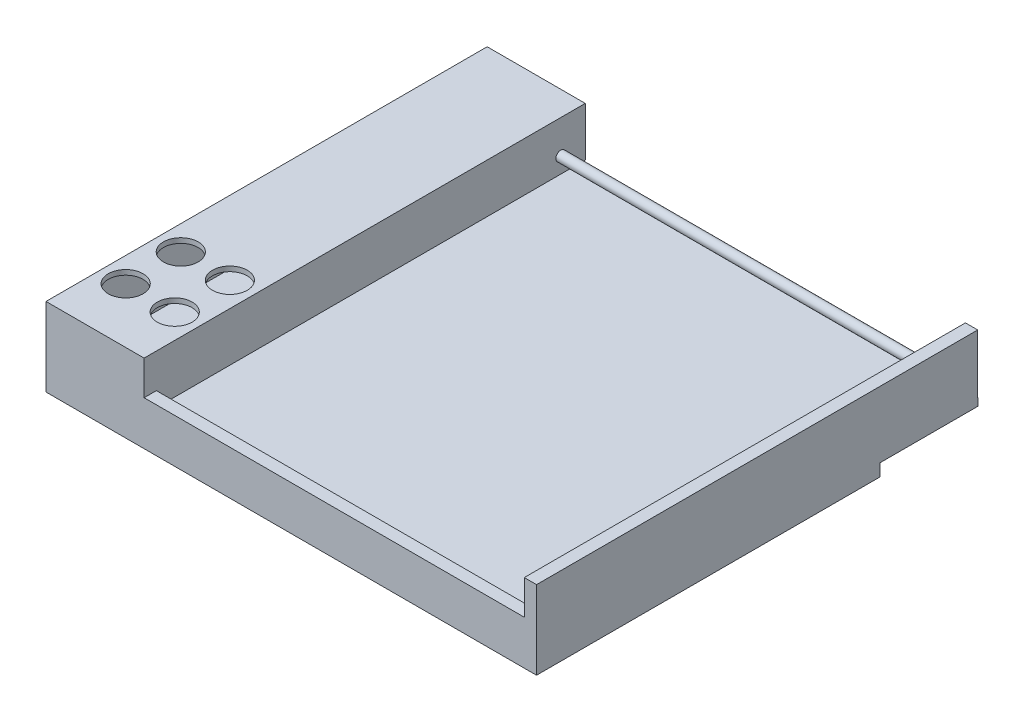
SolidWorks part; units mm, degrees
ref_plane "Front Plane" through (0, 0, 0) normal (0, 0, 1) x (1, 0, 0)
ref_plane "Top Plane" through (0, 0, 0) normal (0, 1, 0) x (1, 0, 0)
ref_plane "Right Plane" through (0, 0, 0) normal (1, 0, 0) x (0, 0, -1)
sketch "Sketch1" plane through (0, 0, 0) normal (0, 1, 0) x (1, 0, 0)
  line L1 (-100, -90) -> (100, -90)
  line L2 (-100, -90) -> (-100, 90)
  line L3 (-100, 90) -> (100, 90)
  line L4 (100, -90) -> (100, 90)
  line L5 (-100, -90) -> (100, 90) construction
  line L6 (-100, 90) -> (100, -90) construction
  point P0 (0, 0)
  dimension "D1" = 200
  dimension "D2" = 180
extrude "Boss-Extrude1" add sketch "Sketch1" along normal blind 3
sketch "Sketch2" plane through (0, 0, 0) normal (0, -1, 0) x (1, 0, 0)
  line L0 (-100, 90) -> (100, 90)
  line L1 (-100, 90) -> (-100, -50)
  line L2 (100, 90) -> (100, -50)
  line L3 (-100, -50) -> (100, -50)
  dimension "D1" = 140
extrude "Boss-Extrude2" add sketch "Sketch2" along normal blind 5
sketch "Sketch6" plane through (0, 3, 0) normal (0, 1, 0) x (1, 0, 0)
  line L0 (-100, -90) -> (100, -90)
  line L1 (-100, -90) -> (-100, 89.8697)
  line L2 (100, -90) -> (100, 89.8697)
  line L3 (-100, 89.8697) -> (100, 89.8697)
extrude "Boss-Extrude3" add sketch "Sketch6" along normal blind 24
sketch "Sketch7" plane through (0, 0, -89.8697) normal (0, 0, -1) x (-1, 0, 0)
  line L0 (-100, 15) -> (100, 15) construction
  line L1 (-100, 27) -> (-100, 3) construction
  line L2 (100, 27) -> (100, 3) construction
  line L3 (-100, 27) -> (100, 27) construction
  line L4 (-95, 3) -> (60, 3)
  line L5 (-95, 3) -> (-95, 27)
  line L6 (-95, 27) -> (60, 27)
  line L7 (60, 3) -> (60, 27)
  line L8 (-95, 3) -> (60, 27) construction
  line L9 (-95, 27) -> (60, 3) construction
  point P6 (-17.5, 15)
  dimension "D1" = 155
  dimension "D2" = 5
extrude "Cut-Extrude1" cut sketch "Sketch7" against normal up to surface (179.8697 mm away) up to face at (0, 11, 90)
sketch "Sketch8" plane through (95, 0, 0) normal (-1, 0, 0) x (0, 0, 1)
  line L0 (90, 3) -> (-89.8697, 3) construction
  line L1 (-89.8697, 27) -> (-89.8697, 3) construction
  circle A0 centre (-79.8697, 13.5) radius 2
  dimension "D3" = 4
  dimension "D1" = 10.5
  dimension "D2" = 10
extrude "Boss-Extrude4" add sketch "Sketch8" along normal up to surface (155 mm away) up to face at (-60, 15, 0.0651)
sketch "Sketch9" plane through (0, 3, 0) normal (0, 1, 0) x (1, 0, 0)
  line L0 (95, -90) -> (95, 89.8697) construction
  line L1 (-60, -90) -> (95, -90)
  line L2 (-60, -90) -> (-60, -85)
  line L3 (-60, -85) -> (95, -85)
  line L4 (95, -90) -> (95, -85)
  dimension "D1" = 5
extrude "Boss-Extrude5" add sketch "Sketch9" along normal blind 10
sketch "Sketch11" plane through (0, 0, -89.8697) normal (0, 0, -1) x (-1, 0, 0)
  line L0 (60, 3) -> (98, 3)
  line L1 (60, 3) -> (100, 3) construction
  line L2 (98, 3) -> (98, 25)
  line L3 (98, 25) -> (62, 25)
  line L4 (62, 25) -> (62, 7)
  line L5 (62, 7) -> (60, 7)
  line L6 (60, 3) -> (60, 27) construction
  line L7 (60, 7) -> (60, 3)
  line L8 (60, 27) -> (100, 27) construction
  line L9 (100, 27) -> (100, 3) construction
  dimension "D1" = 4
  dimension "D2" = 2
  dimension "D3" = 2
  dimension "D4" = 2
extrude "Cut-Extrude3" cut sketch "Sketch11" against normal offset from surface (176.8697 mm away) 3 up to face at (8.75, 15.5, 90)
sketch "Sketch12" plane through (0, 27, 0) normal (0, 1, 0) x (1, 0, 0)
  line L0 (-80, 89.8697) -> (-80, -90) construction
  line L1 (-60, 89.8697) -> (-100, 89.8697) construction
  line L2 (-100, -90) -> (-60, -90) construction
  line L3 (-100, -0.0651) -> (-60, -0.0651) construction
  line L4 (-100, 89.8697) -> (-100, -90) construction
  line L5 (-60, -90) -> (-60, 89.8697) construction
  line L6 (-60, -0.0651) -> (-100, -90) construction
  line L7 (-100, -0.0651) -> (-60, -90) construction
  line L8 (-80, -45.0326) -> (-100, -45.0326) construction
  line L9 (-80, -45.0326) -> (-60, -45.0326) construction
  circle A0 centre (-70, -45.0326) radius 7.1
  circle A1 centre (-70, -67.5163) radius 7.1
  circle A2 centre (-90, -67.5163) radius 7.1
  circle A3 centre (-90, -45.0326) radius 7.1
  point P12 (-80, -45.0326)
  dimension "D1" = 14.2
extrude "Cut-Extrude4" cut sketch "Sketch12" against normal up to surface (2 mm away) up to face at (-80, 25, -1.4349)
